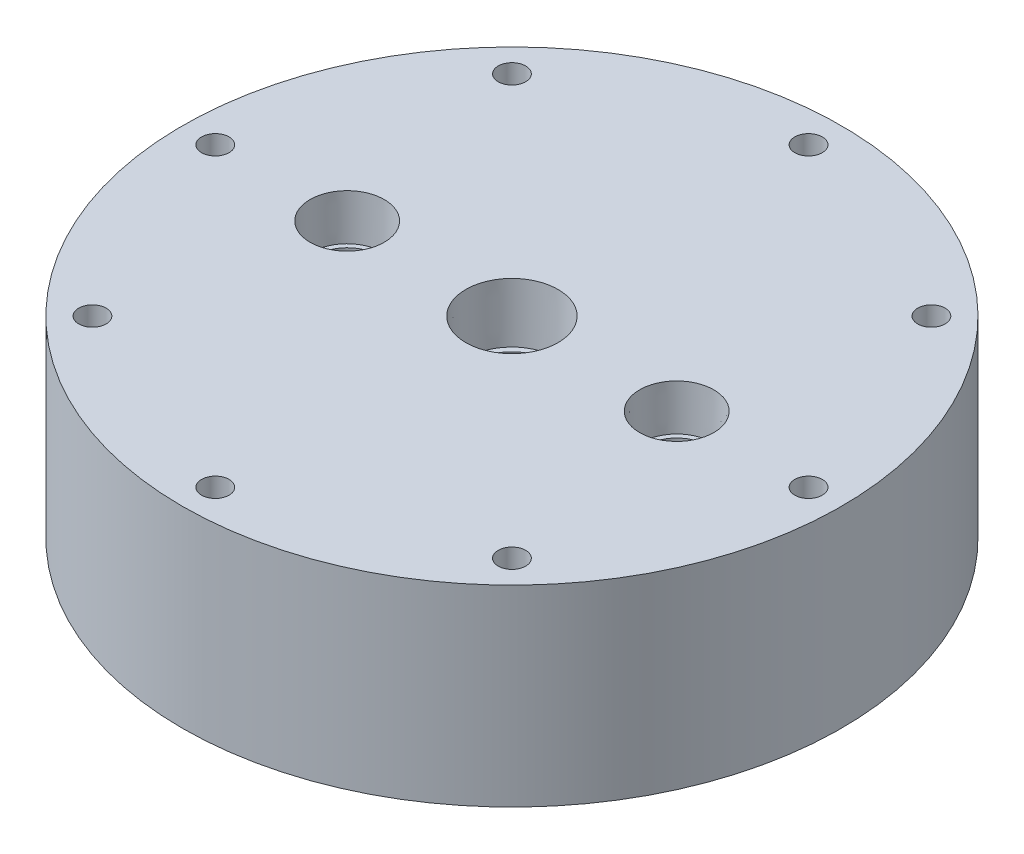
SolidWorks part; units mm, degrees
material "AISI 304"
ref_plane "Front Plane" through (0, 0, 0) normal (0, 0, 1) x (1, 0, 0)
ref_plane "Top Plane" through (0, 0, 0) normal (0, 1, 0) x (1, 0, 0)
ref_plane "Right Plane" through (0, 0, 0) normal (1, 0, 0) x (0, 0, -1)
sketch "Main Shape Profile" plane through (0, 0, 0) normal (0, 0, 1) x (1, 0, 0)
  line L0 (0, 0) -> (0, -35002.3512) construction
  line L1 (0, 44.45) -> (0, 22.86)
  line L2 (0, 22.86) -> (22.225, 22.86)
  line L3 (22.225, 22.86) -> (22.225, 12.7)
  line L5 (28.575, 12.7) -> (28.575, 6.35)
  line L6 (28.575, 6.35) -> (57.15, 6.35)
  line L7 (57.15, 6.35) -> (57.15, 0)
  line L8 (57.15, 0) -> (76.2, 0)
  line L9 (76.2, 0) -> (76.2, 44.45)
  line L10 (76.2, 44.45) -> (0, 44.45)
  line L11 (22.225, 12.7) -> (25.4, 12.7)
  line L12 (25.4, 12.7) -> (25.4, 14.732)
  line L13 (25.4, 14.732) -> (27.432, 14.732)
  line L14 (27.432, 14.732) -> (27.432, 12.7)
  line L15 (27.432, 12.7) -> (28.575, 12.7)
  dimension "Outer Flange Diameter" = 152.4
  dimension "Kerosene Plate Thickness" = 6.35
  dimension "LOX Plate Thickness" = 6.35
  dimension "LOX Manifold Thickness" = 10.16
  dimension "Total Shell Thickess" = 44.45
  dimension "Kerosene Plate Outer Diameter" = 114.3
  dimension "LOX Plate Diameter" = 57.15
  dimension "LOX Inner Flange" = 6.35
  dimension "ORing Width" = 2.032
  dimension "ORing Diameter" = 50.8
  dimension "ORing Depth" = 2.032
revolve "Main Shape" add sketch "Main Shape Profile" angle 360 about L0
sketch "Kerosene Inlet Placement Sketch" plane through (0, 44.45, 0) normal (0, 1, 0) x (1, 0, 0)
  line L0 (-38.1, 0) -> (38.1, 0) construction
  point P5 (0, 0)
  dimension "Kerosene Inlet Placement Diameter" = 76.2
hole_wizard "1/2 NPT Tapped Hole1" positions "Sketch2" profile "Sketch3" size "1/2" standard "ANSI Inch" end condition through all
sketch "Sketch2" plane through (0, 44.45, 0) normal (0, 1, 0) x (1, 0, 0)
  point P0 (0, 0)
sketch "Sketch3" plane through (0, 44.45, 0) normal (1, 0, 0) x (0, 0, 1)
  line L0 (0, 0) -> (0, 44.45)
  line L1 (0, 44.45) -> (8.9281, 44.45)
  line L2 (-10.2617, 13.462) -> (-10.6647, 0) construction
  line L3 (8.9281, 44.45) -> (8.9281, 13.462)
  line L4 (8.9281, 13.462) -> (10.2617, 13.462)
  line L5 (10.2617, 13.462) -> (10.6647, 0)
  line L7 (10.6647, 0) -> (0, 0)
  line L8 (0, -6.35) -> (0, 107.95) construction
  line L11 (-8.9281, 13.462) -> (-10.2617, 13.462) construction
  dimension "Thru Tap Drill Dia." = 17.8562
  dimension "Thru Tap Drill Depth" = 44.45
  dimension "Thread Dia." = 21.3295
  dimension "Thread Angle" = 3.43
  dimension "Thread Depth" = 13.462
hole_wizard "3/8 NPT Tapped Hole1" positions "3DSketch1" profile "Sketch4" size "3/8" standard "ANSI Inch" end condition through all
sketch3d "3DSketch1"
  point P0 (-38.1, 44.45, 0)
  point P3 (38.1, 44.45, 0)
sketch "Sketch4" plane through (-38.1, 44.45, 0) normal (1, 0, 0) x (0, 0, 1)
  line L0 (0, 0) -> (0, 44.45)
  line L1 (0, 44.45) -> (7.1374, 44.45)
  line L2 (-8.2632, 10.414) -> (-8.575, 0) construction
  line L3 (7.1374, 44.45) -> (7.1374, 10.414)
  line L4 (7.1374, 10.414) -> (8.2632, 10.414)
  line L5 (8.2632, 10.414) -> (8.575, 0)
  line L7 (8.575, 0) -> (0, 0)
  line L8 (0, -6.35) -> (0, 107.95) construction
  line L11 (-7.1374, 10.414) -> (-8.2632, 10.414) construction
  dimension "Thru Tap Drill Dia." = 14.2748
  dimension "Thru Tap Drill Depth" = 44.45
  dimension "Thread Dia." = 17.15
  dimension "Thread Angle" = 3.43
  dimension "Thread Depth" = 10.414
sketch "Bolt Holes Profile" plane through (0, 44.45, 0) normal (0, 1, 0) x (1, 0, 0)
  line L0 (0, 68.58) -> (0, -68.58) construction
  circle A0 centre (0, 68.58) radius 3.175
  circle A1 centre (48.4934, 48.4934) radius 3.175
  circle A2 centre (68.58, 0) radius 3.175
  circle A3 centre (48.4934, -48.4934) radius 3.175
  circle A4 centre (0, -68.58) radius 3.175
  circle A5 centre (-48.4934, -48.4934) radius 3.175
  circle A6 centre (-68.58, 0) radius 3.175
  circle A7 centre (-48.4934, 48.4934) radius 3.175
  point P5 (0, 0)
  point P21 (0, 0)
  dimension "Bolt Hole Diameter" = 6.35
  dimension "Bolt Hole Placement Diameter" = 137.16
  dimension "Number of Bolts" = 8
extrude "Bolt Holes" cut sketch "Bolt Holes Profile" against normal through all
sketch "Dowel Holes Profile" plane through (0, 6.35, 0) normal (0, -1, 0) x (1, 0, 0)
  line L0 (0, 46.355) -> (0, -46.355) construction
  circle A0 centre (0, 46.355) radius 1.27
  circle A1 centre (0, -46.355) radius 1.27
  point P5 (0, 0)
  dimension "Dowel Hole Diameter" = 2.54
  dimension "Dowel Placement Outer Diameter" = 92.71
extrude "Dowel Holes" cut sketch "Dowel Holes Profile" against normal blind 2.54
